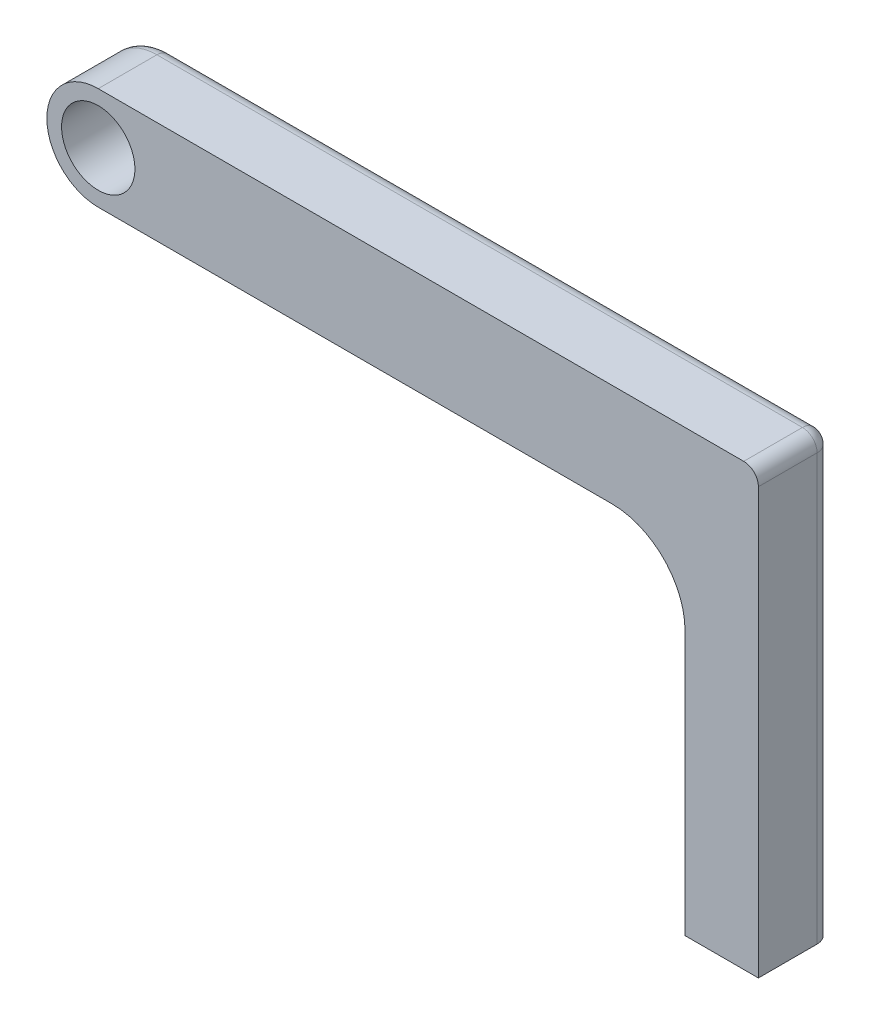
SolidWorks part; units mm, degrees
ref_plane "Front Plane" through (0, 0, 0) normal (0, 0, 1) x (1, 0, 0)
ref_plane "Top Plane" through (0, 0, 0) normal (0, 1, 0) x (1, 0, 0)
ref_plane "Right Plane" through (0, 0, 0) normal (1, 0, 0) x (0, 0, -1)
sketch "Sketch1" plane through (0, 0, 0) normal (0, 0, 1) x (1, 0, 0)
  line L1 (0, -3.5) -> (40, -3.5)
  line L3 (0, 3.5) -> (40, 3.5)
  line L6 (40, 3.5) -> (45, 3.5)
  line L7 (40, -3.5) -> (40, -26.5)
  line L8 (40, -26.5) -> (45, -26.5)
  line L9 (45, 3.5) -> (45, -26.5)
  arc A0 (0, 3.5) -> (0, -3.5) centre (0, 0) ccw
  circle A1 centre (0, 0) radius 2.25
  dimension "D1" = 7
  dimension "D2" = 4.5
  dimension "D4" = 5
  dimension "D3" = 40
  dimension "D5" = 30
extrude "Boss-Extrude1" add sketch "Sketch1" along normal blind 5 contours L3 L6 L9 L8 L7 L1 A0
sketch "Sketch2" plane through (0, 0, 0) normal (0, 0, -1) x (-1, 0, 0)
  circle A0 centre (0, 0) radius 2.5
extrude "Cut-Extrude1" cut sketch "Sketch2" against normal blind 5
fillet "Fillet1" radius 5 1 edges at (40, -3.5, 2.5)
fillet "Fillet2" radius 1 6 edges at (40, -17.5, 0) (38.5355, -4.9645, 0) (17.5, -3.5, 0) (-3.5, 0, 0) (45, -11.5, 0) (22.5, 3.5, 0)
fillet "Fillet3" radius 1 2 edges at (44.7071, 3.2071, 0.2929) (45, 3.5, 3)
